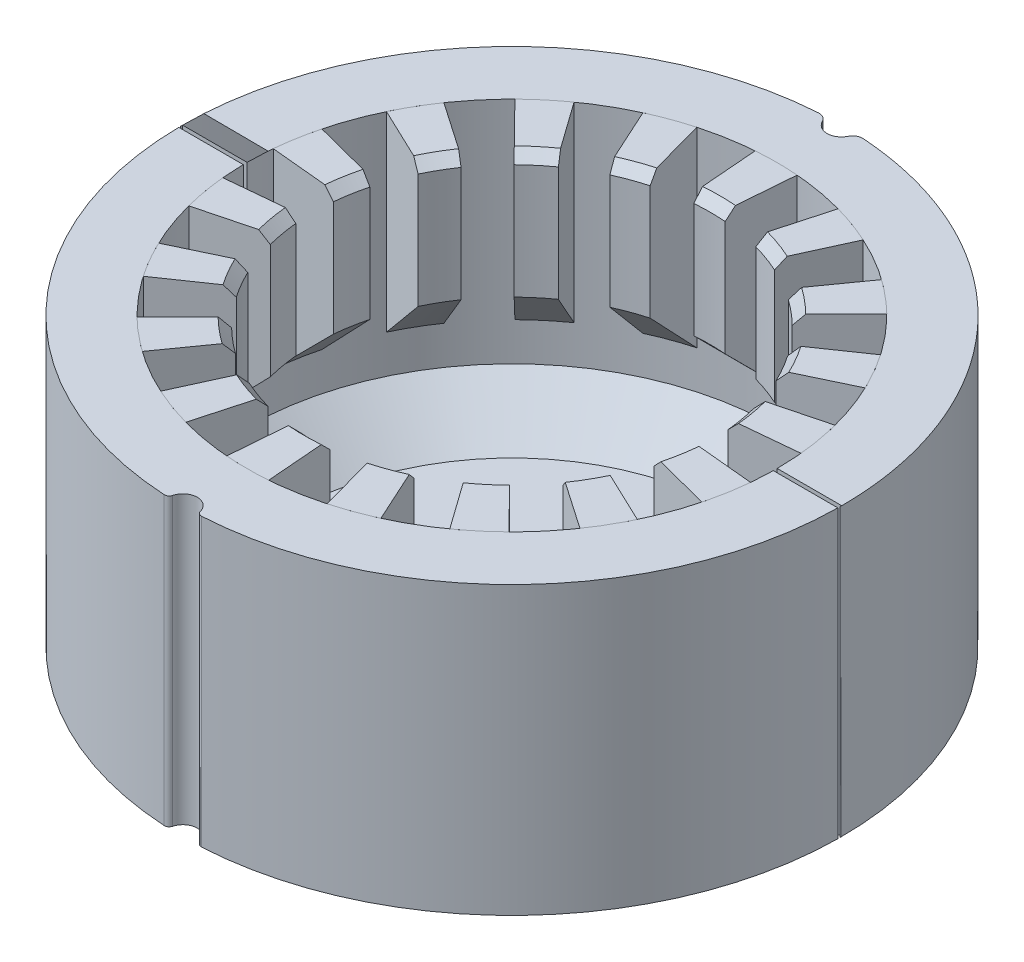
SolidWorks part; units mm, degrees
other "Markup1"
sketch "Sketch4"
other "Markup5"
sketch "Sketch8" plane through (34.5, 25, 34.4428) normal (0.0041, 0.9851, 0.1719) x (0.981, -0.0374, 0.1906)
other "Markup6"
sketch "Sketch9" plane through (34.5, 25, 34.4428) normal (0.0041, 0.9851, 0.1719) x (0.981, -0.0374, 0.1906)
other "Markup7"
sketch "Sketch10" plane through (-34.5, 25, 34.4428) normal (-0.125, 0.9874, 0.0969) x (0.5933, -0.0039, 0.805)
ref_plane "Front Plane" through (0, 0, 0) normal (0, 0, 1) x (1, 0, 0)
ref_plane "Top Plane" through (0, 0, 0) normal (0, 1, 0) x (1, 0, 0)
ref_plane "Right Plane" through (0, 0, 0) normal (1, 0, 0) x (0, 0, -1)
sketch "Sketch1" plane through (0, 0, 0) normal (0, 1, 0) x (1, 0, 0)
  line L3 (0, 0.002) -> (0, 3.7877) construction
  line L4 (0, 3.7877) -> (2.417, 3.7877)
  line L5 (0, 3.7877) -> (-2.417, 3.7877)
  arc A0 (1.9642, -34.442) -> (34.1982, 4.5552) centre (0, 0.002) ccw
  arc A2 (-2.417, 3.7877) -> (2.417, 3.7877) centre (0, 0.002) ccw
  circle A3 centre (0, 0.002) radius 34.5 construction
  arc A7 (-1.3541, 33.8562) -> (1.3541, 33.8562) centre (0, 34.5015) ccw
  arc A8 (34.1982, 4.5552) -> (2.3241, 34.4236) centre (0, 0.002) ccw
  arc A9 (-2.3241, 34.4236) -> (-34.1982, 4.5552) centre (0, 0.002) ccw
  arc A10 (-34.1982, 4.5552) -> (-1.9642, -34.442) centre (0, 0.002) ccw
  arc A11 (1.3541, 33.8562) -> (2.3241, 34.4236) centre (2.2568, 33.4259) cw
  arc A12 (-1.3541, 33.8562) -> (-2.3241, 34.4236) centre (-2.2568, 33.4259) ccw
  arc A13 (1.4518, -34.0686) -> (-1.4518, -34.0686) centre (0, -34.4457) ccw
  arc A14 (1.4518, -34.0686) -> (1.9642, -34.442) centre (1.9358, -33.9428) ccw
  arc A15 (-1.4518, -34.0686) -> (-1.9642, -34.442) centre (-1.9358, -33.9428) cw
  point P15 (1.4997, 34.4694)
  dimension "D2" = 4.834
  dimension "D3" = 4.4915
  dimension "D4" = 34.5
  dimension "D5" = 1
  dimension "D6" = 1.5
  dimension "D7" = 0.5
  dimension "D11" = 1.4997
sketch "Sketch2" plane through (0, 0, 0) normal (0, 1, 0) x (1, 0, 0)
  line L0 (0, 27.75) -> (0, 20.75) construction
  line L1 (-2.1983, 27.6628) -> (0, 27.75) construction
  line L2 (0, 27.75) -> (2.1983, 27.6628) construction
  line L3 (-2.1983, 27.6628) -> (-1.6438, 20.6848)
  line L6 (1.6438, 20.6848) -> (2.1983, 27.6628)
  line L7 (-1.6438, 20.6848) -> (0, 0) construction
  line L8 (0, 0) -> (1.6438, 20.6848) construction
  circle A16 centre (0, 0) radius 27.75
  arc A18 (-1.6438, 20.6848) -> (1.6438, 20.6848) centre (0, 0) cw
  point P3 (0, 20.75)
  point P8 (0, 0)
  point P10 (-2.4975, 20.75)
  point P11 (0, 0)
  dimension "D1" = 55.5
  dimension "D2" = 2.2
  dimension "D3" = 7
extrude "Boss-Extrude1" add sketch "Sketch1" along normal blind 30 contours A10 A0 A8 A7 A9 A2 L5 L4 | L5 A2 L4 region at (0, 0, 0.1522) region at (2.2155, 0, 33.5591)
extrude "Cut-Extrude2" cut sketch "Sketch2" along normal up to next from offset 1 contours A16 | A16 region at (0, 0, 0.2745)
extrude "Boss-Extrude2" add sketch "Sketch2<2>" along normal up to surface (30 mm away) from offset 10 separate body contours A16 region at (0, 0, -24.3928) up to face at (0, 30, 27.75)
sketch "Sketch2<2>" plane through (0, 0, 0) normal (0, 1, 0) x (1, 0, 0) same geometry as "Sketch2"
chamfer "Chamfer2" distance 1 angle 45 1 edges at (0, 30, -20.75)
chamfer "Chamfer3" distance 7 angle 45 1 edges at (0, 10, -20.75)
pattern_circular "CirPattern2" count 18 over 360 about axis through (0, 30, 0) along (0, 1, 0) of bodies 106
fillet "Fillet2" radius 5 1 edges at (0, 1, 27.75) profile chamfer
sketch "Sketch14" plane through (0, 30, 0) normal (0, 1, 0) x (1, 0, 0)
  line L0 (34.4995, -0.1783) -> (-34.4995, -0.1783) construction
  line L1 (-34.4995, 0.0217) -> (-34.4995, -0.3783)
  line L2 (-34.4995, 0.0217) -> (34.4995, 0.0217)
  line L3 (34.4995, 0.0217) -> (34.4995, -0.3783)
  line L4 (34.4995, -0.3783) -> (-34.4995, -0.3783)
  arc A0 (1.9642, -34.442) -> (2.3241, 34.4236) centre (0, 0.002) ccw construction
  arc A1 (-2.3241, 34.4236) -> (-1.9642, -34.442) centre (0, 0.002) ccw construction
  point P12 (-34.4995, -0.1783)
  point P14 (34.4995, -0.1783)
  dimension "D1" = 0.4
extrude "Cut-Extrude4" cut sketch "Sketch14" against normal through all
